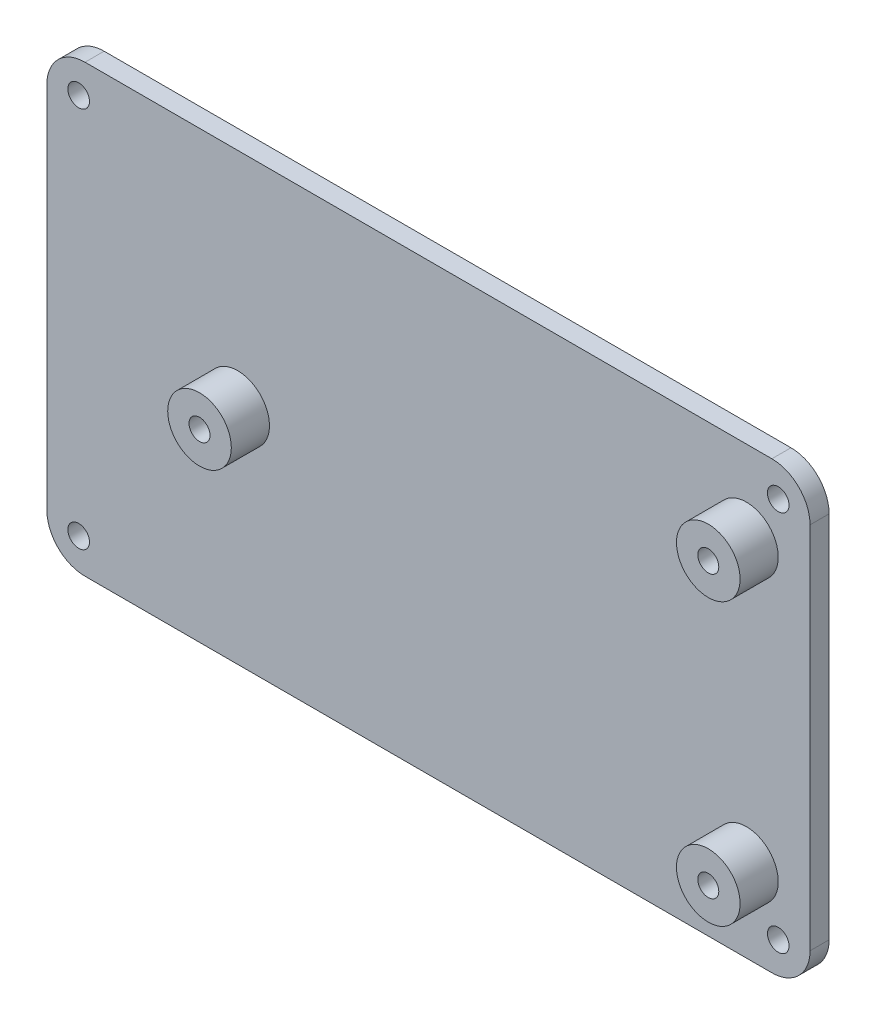
SolidWorks part; units mm, degrees
material "ABS"
ref_plane "前基準面" through (0, 0, 0) normal (0, 0, 1) x (1, 0, 0)
ref_plane "上基準面" through (0, 0, 0) normal (0, 1, 0) x (1, 0, 0)
ref_plane "右基準面" through (0, 0, 0) normal (1, 0, 0) x (0, 0, -1)
sketch "草圖1" plane through (0, 0, 0) normal (0, 0, 1) x (1, 0, 0)
  line L1 (-60, -35) -> (60, -35)
  line L2 (-60, -35) -> (-60, 35)
  line L3 (-60, 35) -> (60, 35)
  line L4 (60, -35) -> (60, 35)
  line L5 (-60, -35) -> (60, 35) construction
  line L6 (-60, 35) -> (60, -35) construction
  point P0 (0, 0)
  dimension "D1" = 120
  dimension "D2" = 70
extrude "填料-伸長1" add sketch "草圖1" along normal blind 3
sketch "草圖2" plane through (0, 0, 3) normal (0, 0, 1) x (1, 0, 0)
  line L0 (0, 0) -> (10, 0) construction
  line L2 (50, 22.1) -> (-30, 22.1) construction
  line L3 (50, 22.1) -> (50, -22.1) construction
  line L4 (50, -22.1) -> (-30, -22.1) construction
  line L5 (-30, 22.1) -> (-30, -22.1) construction
  line L6 (50, 22.1) -> (-30, -22.1) construction
  line L7 (50, -22.1) -> (-30, 22.1) construction
  circle A0 centre (50, 22.1) radius 5
  circle A1 centre (50, -22.1) radius 5
  circle A2 centre (-30, 0) radius 5
  dimension "D3" = 10
  dimension "D1" = 80
  dimension "D2" = 44.2
  dimension "D4" = 10
extrude "填料-伸長2" add sketch "草圖2" along normal blind 6
hole_wizard "M4x0.7 螺紋孔1" positions "草圖3" profile "草圖4" tap size "M4x0.7" standard "Ansi Metric" end condition through all
sketch "草圖3" plane through (0, 0, 9) normal (0, 0, 1) x (1, 0, 0)
  point P0 (-30, 0)
  point P3 (50, 22.1)
  point P6 (50, -22.1)
sketch "草圖4" plane through (-30, 0, 9) normal (1, 0, 0) x (0, -1, 0)
  line L0 (0, 0) -> (0, 9)
  line L1 (0, 9) -> (1.65, 9)
  line L2 (1.65, 9) -> (1.65, 0)
  line L5 (1.65, 0) -> (0, 0)
  line L11 (0, -6.35) -> (0, 107.95) construction
  dimension "貫穿螺孔鑽直徑" = 3.3
  dimension "貫穿螺孔鑽深度" = 9
hole_wizard "M3 餘隙孔1" positions "草圖5" profile "草圖6" hole size "M3" standard "Ansi Metric" end condition through all
sketch "草圖5" plane through (0, 0, 3) normal (0, 0, 1) x (1, 0, 0)
  line L1 (-55, -30) -> (55, -30) construction
  line L2 (-55, -30) -> (-55, 30) construction
  line L3 (-55, 30) -> (55, 30) construction
  line L4 (55, -30) -> (55, 30) construction
  line L5 (-55, -30) -> (55, 30) construction
  line L6 (-55, 30) -> (55, -30) construction
  point P1 (55, 30)
  point P94 (-55, -30)
  point P95 (-55, 30)
  point P96 (55, -30)
  dimension "D1" = 110
  dimension "D2" = 60
sketch "草圖6" plane through (55, 30, 3) normal (1, 0, 0) x (0, -1, 0)
  line L0 (0, 0) -> (0, 3)
  line L1 (0, 3) -> (1.7, 3)
  line L2 (1.7, 3) -> (1.7, 0)
  line L5 (1.7, 0) -> (0, 0)
  line L11 (0, -6.35) -> (0, 107.95) construction
  dimension "貫穿孔直徑" = 3.4
  dimension "貫穿孔深度" = 3
fillet "圓角1" radius 6 4 edges at (-60, -35, 1.5) (-60, 35, 1.5) (60, -35, 1.5) (60, 35, 1.5)
